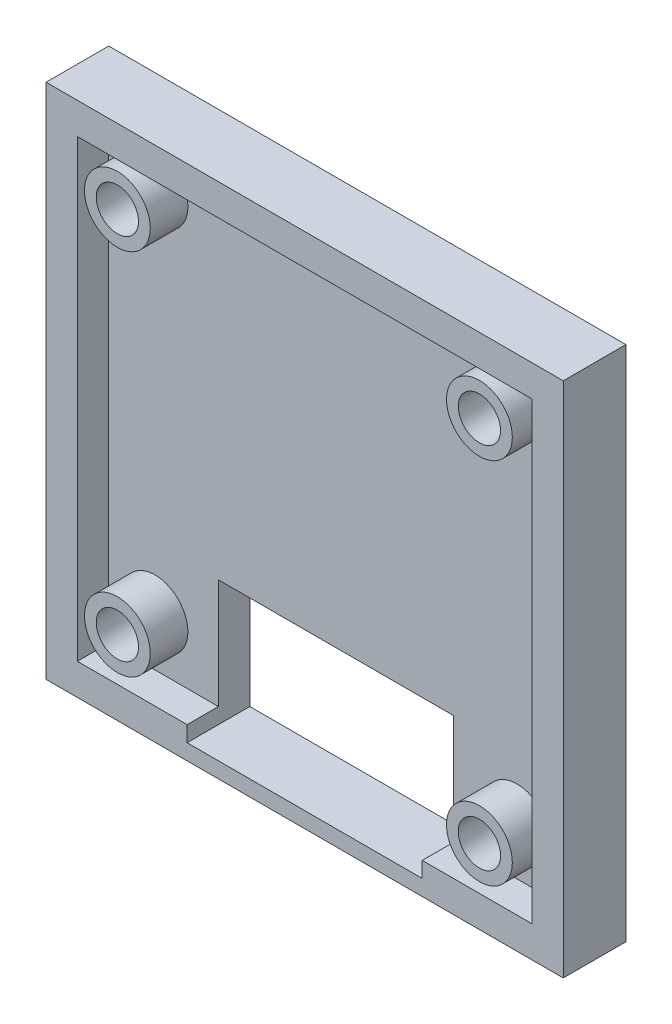
SolidWorks part; units mm, degrees
ref_plane "Front Plane" through (0, 0, 0) normal (0, 0, 1) x (1, 0, 0)
ref_plane "Top Plane" through (0, 0, 0) normal (0, 1, 0) x (1, 0, 0)
ref_plane "Right Plane" through (0, 0, 0) normal (1, 0, 0) x (0, 0, -1)
sketch "Sketch1" plane through (0, 0, 0) normal (0, 0, 1) x (1, 0, 0)
  line L0 (0, -7.5) -> (0, -15.5) construction
  line L1 (16.5, -16.5) -> (-16.5, -16.5)
  line L2 (16.5, -16.5) -> (16.5, 16.5)
  line L3 (16.5, 16.5) -> (-16.5, 16.5)
  line L4 (-16.5, -16.5) -> (-16.5, 16.5)
  line L5 (16.5, -16.5) -> (-16.5, 16.5) construction
  line L6 (16.5, 16.5) -> (-16.5, -16.5) construction
  line L7 (-11.55, -11.35) -> (11.55, -11.35)
  line L8 (-11.55, -11.35) -> (-11.55, 12.15)
  line L9 (-11.55, 12.15) -> (11.55, 12.15)
  line L10 (11.55, -11.35) -> (11.55, 12.15)
  line L11 (-11.55, -11.35) -> (11.55, 12.15) construction
  line L12 (-11.55, 12.15) -> (11.55, -11.35) construction
  line L17 (-7.5, -7.5) -> (7.5, -7.5)
  line L18 (-7.5, -7.5) -> (-7.5, -15.5)
  line L19 (-7.5, -15.5) -> (7.5, -15.5)
  line L20 (7.5, -7.5) -> (7.5, -15.5)
  circle A0 centre (-11.55, 12.15) radius 1.35
  circle A1 centre (11.55, 12.15) radius 1.35
  circle A2 centre (-11.55, -11.35) radius 1.35
  circle A3 centre (11.55, -11.35) radius 1.35
  point P0 (0, 0)
  point P6 (0, 0.4)
  point P21 (0, 0)
  point P22 (0, 0)
  point P23 (0, 0)
  point P24 (0, 0)
  point P25 (0, 0)
  point P26 (0, 0)
  point P27 (0, 0)
  point P28 (0, 0)
  dimension "D7" = 2.7
  dimension "D1" = 23.1
  dimension "D2" = 23.5
  dimension "D3" = 0.4
  dimension "D5" = 33
  dimension "D6" = 33
  dimension "D8" = 15
  dimension "D9" = 8
  dimension "D10" = 1
extrude "Boss-Extrude1" add sketch "Sketch1" along normal blind 2 contours L4 L1 L2 L3 A3 L7 A2 L8 A0 L9 A1 L10 | A3 L10 A1 L9 A0 L8 A2 L7 L18 L19 L20 region at (0, -16.0333, 0) region at (0, 1.5836, 0)
sketch "Sketch2" plane through (0, 0, 2) normal (0, 0, 1) x (1, 0, 0)
  circle A0 centre (-11.55, 12.15) radius 2.1
  circle A1 centre (-11.55, -11.35) radius 2.1
  circle A2 centre (11.55, -11.35) radius 2.1
  circle A3 centre (11.55, 12.15) radius 2.1
  circle A4 centre (11.55, 12.15) radius 1.1
  circle A5 centre (-11.55, 12.15) radius 1.1
  circle A6 centre (-11.55, -11.35) radius 1.1
  circle A7 centre (11.55, -11.35) radius 1.1
  dimension "D1" = 1
extrude "Boss-Extrude2" add sketch "Sketch2" along normal blind 2.4
sketch "Sketch3" plane through (0, 0, 2) normal (0, 0, 1) x (1, 0, 0)
  line L1 (-16.5, 16.5) -> (16.5, 16.5)
  line L2 (-16.5, 16.5) -> (-16.5, -16.5)
  line L3 (-16.5, -16.5) -> (16.5, -16.5)
  line L4 (16.5, 16.5) -> (16.5, -16.5)
  line L5 (-14.5, 14.5) -> (14.5, 14.5)
  line L6 (-14.5, 14.5) -> (-14.5, -14.5)
  line L7 (-14.5, -14.5) -> (14.5, -14.5)
  line L8 (14.5, 14.5) -> (14.5, -14.5)
  dimension "D1" = 2
  dimension "D2" = 2
  dimension "D3" = 2
  dimension "D4" = 2
extrude "Boss-Extrude3" add sketch "Sketch3" along normal blind 2
sketch "Sketch4" plane through (0, 0, 0) normal (0, 0, -1) x (-1, 0, 0)
  circle A0 centre (-11.55, 12.15) radius 1.35
  circle A1 centre (11.55, 12.15) radius 1.35
  circle A2 centre (11.55, -11.35) radius 1.35
  circle A3 centre (-11.55, -11.35) radius 1.35
extrude "Cut-Extrude1" cut sketch "Sketch4" against normal blind 10
sketch "Sketch5" plane through (0, 0, 0) normal (0, 0, -1) x (-1, 0, 0)
  line L1 (-7.5, -7.5) -> (7.5, -7.5)
  line L2 (-7.5, -7.5) -> (-7.5, -15.5)
  line L3 (-7.5, -15.5) -> (7.5, -15.5)
  line L4 (7.5, -7.5) -> (7.5, -15.5)
extrude "Cut-Extrude2" cut sketch "Sketch5" against normal blind 10
